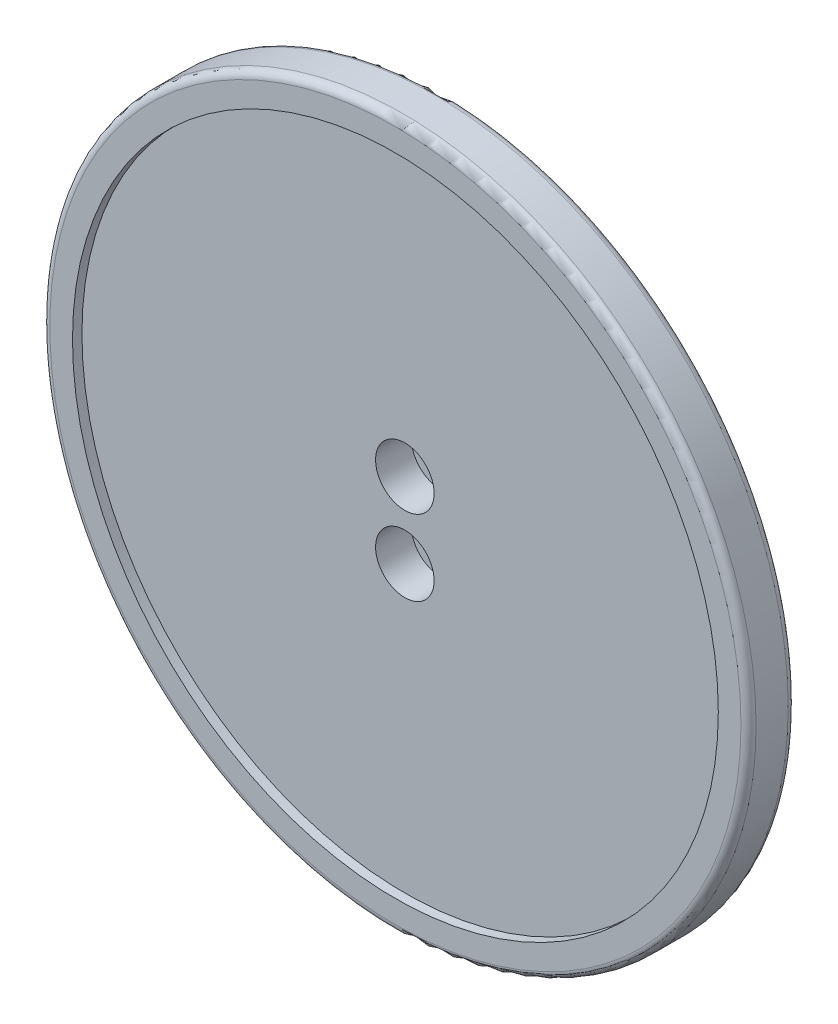
SolidWorks part; units mm, degrees
ref_plane "Front Plane" through (0, 0, 0) normal (1, 0, 0) x (0, 1, 0)
ref_plane "Top Plane" through (0, 0, 0) normal (0, 0, 1) x (0, 1, 0)
ref_plane "Right Plane" through (0, 0, 0) normal (0, 1, 0) x (-1, 0, 0)
sketch "Sketch1" plane through (0, 0, 0) normal (0, 0, 1) x (0, 1, 0)
  circle A0 centre (0, 0) radius 42.75
  circle A1 centre (0, 0) radius 46.75
  dimension "D1" = 85.5
  dimension "D2" = 4
extrude "Boss-Extrude1" add sketch "Sketch1" along normal blind 1.25
sketch "Sketch2" plane through (0, 0, 0) normal (0, 0, -1) x (1, 0, 0)
  line L0 (0, -5) -> (0, 5) construction
  circle A0 centre (0, 0) radius 46.75
  circle A1 centre (0, 5) radius 2.25
  circle A2 centre (0, -5) radius 2.25
  circle A3 centre (0, 0) radius 46.75 construction
  point P5 (0, 0)
  dimension "D1" = 4.5
  dimension "D2" = 10
extrude "Boss-Extrude2" add sketch "Sketch2" along normal blind 5
sketch "Sketch3" plane through (0, 0, 0) normal (0, 0, 1) x (1, 0, 0)
  circle A0 centre (0, 5) radius 3.875
  circle A1 centre (0, -5) radius 3.875
  dimension "D1" = 7.75
extrude "Cut-Extrude1" cut sketch "Sketch3" against normal blind 4.75
sketch "Sketch4" plane through (0, 0, -5) normal (0, 0, -1) x (1, 0, 0)
  line L1 (-6.35, -10) -> (6.35, -10)
  line L2 (-6.35, -10) -> (-6.35, 10)
  line L3 (-6.35, 10) -> (6.35, 10)
  line L4 (6.35, -10) -> (6.35, 10)
  line L5 (-6.35, -10) -> (6.35, 10) construction
  line L6 (-6.35, 10) -> (6.35, -10) construction
  circle A0 centre (0, -5) radius 2.25 construction
  point P0 (0, 0)
  circle M5 centre (0, 5) radius 2.25
  circle M7 centre (0, -5) radius 2.25
  dimension "D2" = 5
  dimension "D1" = 12.7
extrude "Boss-Extrude3" add sketch "Sketch4" along normal blind 18.975 contours L1 L4 L3 L2 M5 M7 region at (0, 0, -5)
fillet "Fillet1" radius 10 4 edges at (0, -10, -5) (-6.35, 0, -5) (0, 10, -5) (6.35, 0, -5)
fillet "Fillet2" radius 1 2 edges at (-46.75, 0, -5) (46.75, 0, 1.25)
fillet "Fillet3" radius 2.5 8 edges at (-9.2789, 12.9289, -7.9289) (9.2789, 12.9289, -7.9289) (-9.2789, -12.9289, -7.9289) (9.2789, -12.9289, -7.9289) (-6.35, 10, -19.4875) (6.35, 10, -19.4875) (-6.35, -10, -19.4875) (6.35, -10, -19.4875)
